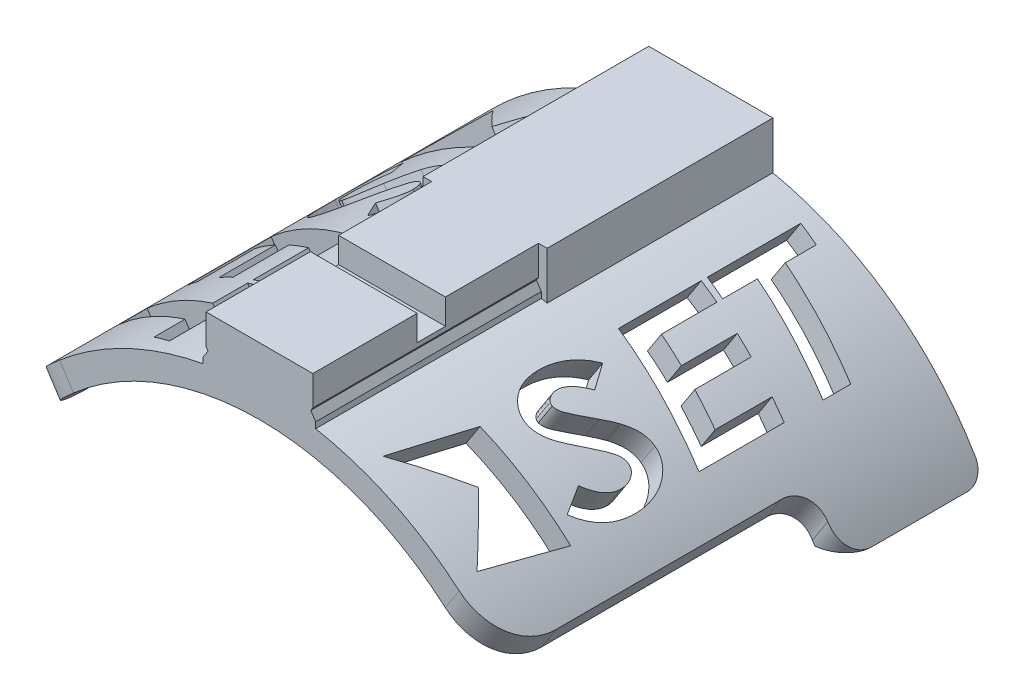
SolidWorks part; units mm, degrees
ref_plane "Plan de face" through (0, 0, 0) normal (0, 0, 1) x (1, 0, 0)
ref_plane "Plan de dessus" through (0, 0, 0) normal (0, 1, 0) x (1, 0, 0)
ref_plane "Plan de droite" through (0, 0, 0) normal (1, 0, 0) x (0, 0, -1)
sketch "Esquisse1" plane through (0, 0, 0) normal (0, 0, 1) x (1, 0, 0)
  line L1 (11, 61.8) -> (11, 53.3784)
  line L2 (-48.556, 24.75) -> (-43.4446, 24.75)
  line L3 (43.4446, 24.75) -> (48.556, 24.75)
  line L4 (-11, 61.8) -> (-11, 53.3784)
  line L7 (-11, 61.8) -> (11, 61.8)
  arc A0 (43.4446, 24.75) -> (-43.4446, 24.75) centre (0, 0) ccw
  arc A1 (48.556, 24.75) -> (11, 53.3784) centre (0, 0) ccw
  arc A2 (-11, 53.3784) -> (-48.556, 24.75) centre (0, 0) ccw
  point P21 (0, 60)
  dimension "D1" = 100
  dimension "D4" = 109
  dimension "D2" = 24.75
  dimension "D3" = 22
  dimension "D5" = 11
  dimension "D6" = 61.8
extrude "Boss.-Extru.1" add sketch "Esquisse1" along normal blind 145
ref_plane "Plan3" through (0, 0, 123.5) normal (0, 0, 1) x (1, 0, 0)
sketch "Esquisse8" plane through (0, 0, 145) normal (0, 0, 1) x (1, 0, 0)
  line L0 (0, 0) -> (0, 89.5038) construction
  line L1 (9.465, 61.8) -> (-9.465, 61.8)
  line L2 (11, 61.8) -> (-11, 61.8) construction
  line L3 (-9.9664, 54.6422) -> (-9.9664, 54.1422)
  line L4 (9.465, 56.52) -> (9.465, 61.8)
  line L5 (9.096, 55.9608) -> (9.465, 56.52)
  line L6 (-9.9664, 54.1422) -> (-11, 54.1422)
  line L7 (9.9664, 54.6422) -> (9.9664, 54.1422)
  line L8 (-9.9664, 54.6422) -> (-9.096, 55.9608)
  line L9 (-9.096, 55.9608) -> (-9.465, 56.52)
  line L10 (-9.465, 56.52) -> (-9.465, 61.8)
  line L11 (9.9664, 54.6422) -> (9.096, 55.9608)
  line L12 (-11, 61.8) -> (-11, 71.017)
  line L15 (-11, 71.017) -> (11, 71.017)
  line L18 (9.9664, 54.1422) -> (11, 54.1422)
  line L559 (-11, 61.8) -> (-11, 53.3784) construction
  line L560 (-11, 61.8) -> (-11, 54.1422)
  line L561 (11, 53.3784) -> (11, 61.8) construction
  line L562 (11, 54.1422) -> (11, 71.017)
  point P19 (10.65, 63.2534)
  point P21 (0, 61.8)
  point P22 (8.5695, 65)
  dimension "D3" = 146.58
  dimension "D1" = 9.465
  dimension "D2" = 5.28
  dimension "D4" = 0.67
  dimension "D5" = 1.58
  dimension "D6" = 113.15
  dimension "D7" = 0.5
extrude "Enlèv. mat.-Extru.5" cut sketch "Esquisse8" against normal blind 40
ref_plane "Plan9" through (0, 0, 126.5) normal (0, 0, 1) x (1, 0, 0)
sketch "Esquisse23" plane through (0, 0, 126.5) normal (0, 0, 1) x (1, 0, 0)
  line L0 (9.465, 61.8) -> (-9.465, 61.8) construction
  line L1 (9.465, 61.8) -> (-9.465, 61.8)
  line L2 (-9.465, 56.52) -> (-9.465, 61.8) construction
  line L3 (-9.465, 57.3) -> (-9.465, 61.8)
  line L4 (9.465, 61.8) -> (9.465, 56.52) construction
  line L5 (9.465, 61.8) -> (9.465, 57.3)
  line L6 (-9.465, 57.3) -> (9.465, 57.3)
  dimension "D1" = 4.5
extrude "Enlèv. mat.-Extru.8" cut sketch "Esquisse23" against normal blind 5
shell "Coque7" thickness 2.5 removed face at (0, 45.3956, 0)
sketch "Esquisse24" plane through (0, 0, 105) normal (0, 0, 1) x (1, 0, 0)
  line L1 (11, 53.3784) -> (11, 54.1422) construction
  line L2 (9.9664, 54.1422) -> (11, 54.1422) construction
  line L3 (9.9664, 54.1422) -> (11, 54.1422)
  line L5 (11, 53.3784) -> (11, 54.1422)
  line L6 (9.9664, 54.6422) -> (9.9664, 54.1422) construction
  line L7 (9.9664, 53.581) -> (9.9664, 54.1422)
  line L8 (-11, 54.1422) -> (-9.9664, 54.1422) construction
  line L9 (-11, 54.1422) -> (-9.9664, 54.1422)
  line L10 (-11, 61.8) -> (-11, 54.1422) construction
  line L11 (-11, 54.1422) -> (-11, 53.3784)
  line L14 (-9.9664, 54.1422) -> (-9.9664, 54.6422) construction
  line L17 (-9.9664, 54.1422) -> (-9.9664, 53.581)
  arc A0 (48.556, 24.75) -> (11, 53.3784) centre (0, 0) ccw construction
  arc A1 (-9.9664, 53.581) -> (-11, 53.3784) centre (0, 0) ccw
  arc A2 (11, 53.3784) -> (9.9664, 53.581) centre (0, 0) ccw
extrude "Enlèv. mat.-Extru.9" cut sketch "Esquisse24" along normal up to surface (40 mm away) up to face at (0, 50.7766, 145)
sketch "Esquisse16" plane through (0, 0, 0) normal (0, 0, -1) x (-1, 0, 0)
  line L8 (11, 61.8) -> (-11, 61.8)
  line L9 (-11, 61.8) -> (-11, 53.3784)
  line L10 (-48.556, 24.75) -> (-43.4446, 24.75)
  line L11 (43.4446, 24.75) -> (48.556, 24.75)
  line L12 (11, 53.3784) -> (11, 61.8)
  line L16 (11, 61.8) -> (-11, 61.8)
  line L17 (-11, 61.8) -> (-11, 53.3784)
  line L18 (-48.556, 24.75) -> (-43.4446, 24.75)
  line L19 (43.4446, 24.75) -> (48.556, 24.75)
  line L20 (11, 53.3784) -> (11, 61.8)
  arc A3 (48.556, 24.75) -> (11, 53.3784) centre (0, 0) ccw
  arc A4 (-11, 53.3784) -> (-48.556, 24.75) centre (0, 0) ccw
  arc A5 (43.4446, 24.75) -> (-43.4446, 24.75) centre (0, 0) ccw
  arc A6 (48.556, 24.75) -> (11, 53.3784) centre (0, 0) ccw
  arc A8 (-11, 53.3784) -> (-48.556, 24.75) centre (0, 0) ccw
  arc A9 (43.4446, 24.75) -> (-43.4446, 24.75) centre (0, 0) ccw
  dimension "D1" = 0
extrude "Boss.-Extru.7" add sketch "Esquisse16" against normal blind 2
sketch "Esquisse19" plane through (0, 0, 145) normal (0, 0, 1) x (1, 0, 0)
  line L0 (0, 0) -> (-43.2339, 66.5744) construction
  line L1 (0, 0) -> (46.349, 71.3712) construction
  line L3 (0, 0) -> (0, 45.194) construction
  dimension "D1" = 33
  dimension "D2" = 33
ref_plane "Plan7" through (-29.6828, 45.7075, 0) normal (-0.5446, 0.8387, 0) x (-0.8387, -0.5446, 0)
ref_plane "Plan8" through (29.6828, 45.7075, 0) normal (0.5446, 0.8387, 0) x (-0.8387, 0.5446, 0)
sketch "Esquisse20" plane through (29.6828, 45.7075, 0) normal (0.5446, 0.8387, 0) x (-0.8387, 0.5446, 0)
  line L0 (-9.219, 124.4328) -> (-9.219, 14.1377) construction
  line L1 (9.8559, 126.8177) -> (-9.219, 126.8177)
  line L2 (9.8559, 126.8177) -> (12.9058, 141.0931)
  line L3 (12.9058, 141.0931) -> (3.0312, 133.2862)
  line L4 (3.0312, 133.2862) -> (-6.1691, 141.0931)
  line L5 (-9.219, 126.8177) -> (-6.1691, 141.0931)
  text T0 "<b><i>SET</i></b>" font "Century Gothic" height in points 80
extrude "Enlèv. mat.-Extru.6" cut sketch "Esquisse20" against normal blind 10
ref_plane "Plan10" through (0, 0, 105) normal (0, 0, 1) x (1, 0, 0)
ref_axis "Axe3" through (0, 22.8975, 105) along (0, 1, 0)
pattern_circular "Répétition circulaire1" count 2 over 360 about axis through (0, 22.8975, 105) along (0, 1, 0) of "Enlèv. mat.-Extru.6"
ref_plane "Plan11" through (0, 0, 65) normal (0, 0, 1) x (1, 0, 0)
sketch "Esquisse25" plane through (0, 0, 65) normal (0, 0, 1) x (1, 0, 0)
  line L0 (11, 61.8) -> (-11, 61.8) construction
  line L1 (48.556, 61.8) -> (-48.556, 61.8)
  line L2 (48.556, 61.8) -> (48.556, 24.75)
  line L3 (48.556, 24.75) -> (-48.556, 24.75)
  line L4 (-48.556, 61.8) -> (-48.556, 24.75)
  line L5 (43.4446, 24.75) -> (48.556, 24.75) construction
extrude "Enlèv. mat.-Extru.10" cut sketch "Esquisse25" against normal up to vertex (65 mm away) up to point (-48.556, 24.75, 0)
sketch "Esquisse28" plane through (29.6828, 45.7075, 0) normal (0.5446, 0.8387, 0) x (-0.8387, 0.5446, 0)
  line L1 (-7.1427, 145) -> (5.792, 145)
  line L3 (-17.1427, 95) -> (-17.1427, 135)
  line L5 (-22.1427, 90) -> (-22.2427, 90)
  line L7 (-27.2427, 85) -> (-27.2427, 65)
  line L9 (-27.2427, 65) -> (-34.208, 65)
  line L11 (-34.208, 65) -> (-34.208, 155)
  line L13 (5.792, 145) -> (5.792, 155)
  line L15 (-34.208, 155) -> (5.792, 155)
  arc A1 (-7.1427, 145) -> (-17.1427, 135) centre (-7.1427, 135) ccw
  arc A3 (-22.1427, 90) -> (-17.1427, 95) centre (-22.1427, 95) ccw
  arc A5 (-22.2427, 90) -> (-27.2427, 85) centre (-22.2427, 85) ccw
extrude "Enlèv. mat.-Extru.12" cut sketch "Esquisse28" against normal through all
mirror "Symétrie1" about plane through (0, 0, 0) normal (1, 0, 0) of "Enlèv. mat.-Extru.12"
sketch "Esquisse29" plane through (0, 0, 65) normal (0, 0, -1) x (-1, 0, 0)
  line L0 (-11, 61.8) -> (-11, 53.3784) construction
  line L1 (-11, 61.8) -> (-11, 48.775)
  line L2 (-11, 61.8) -> (11, 61.8) construction
  line L3 (-11, 61.8) -> (11, 61.8)
  line L4 (11, 53.3784) -> (11, 61.8) construction
  line L5 (11, 48.775) -> (11, 61.8)
  arc A0 (43.4446, 24.75) -> (-43.4446, 24.75) centre (0, 0) ccw construction
  arc A1 (11, 48.775) -> (-11, 48.775) centre (0, 0) ccw
extrude "Boss.-Extru.8" add sketch "Esquisse29" against normal blind 3
fillet "Congé1" radius 3 2 edges at (-46.0003, 24.75, 65) (46.0003, 24.75, 65)
